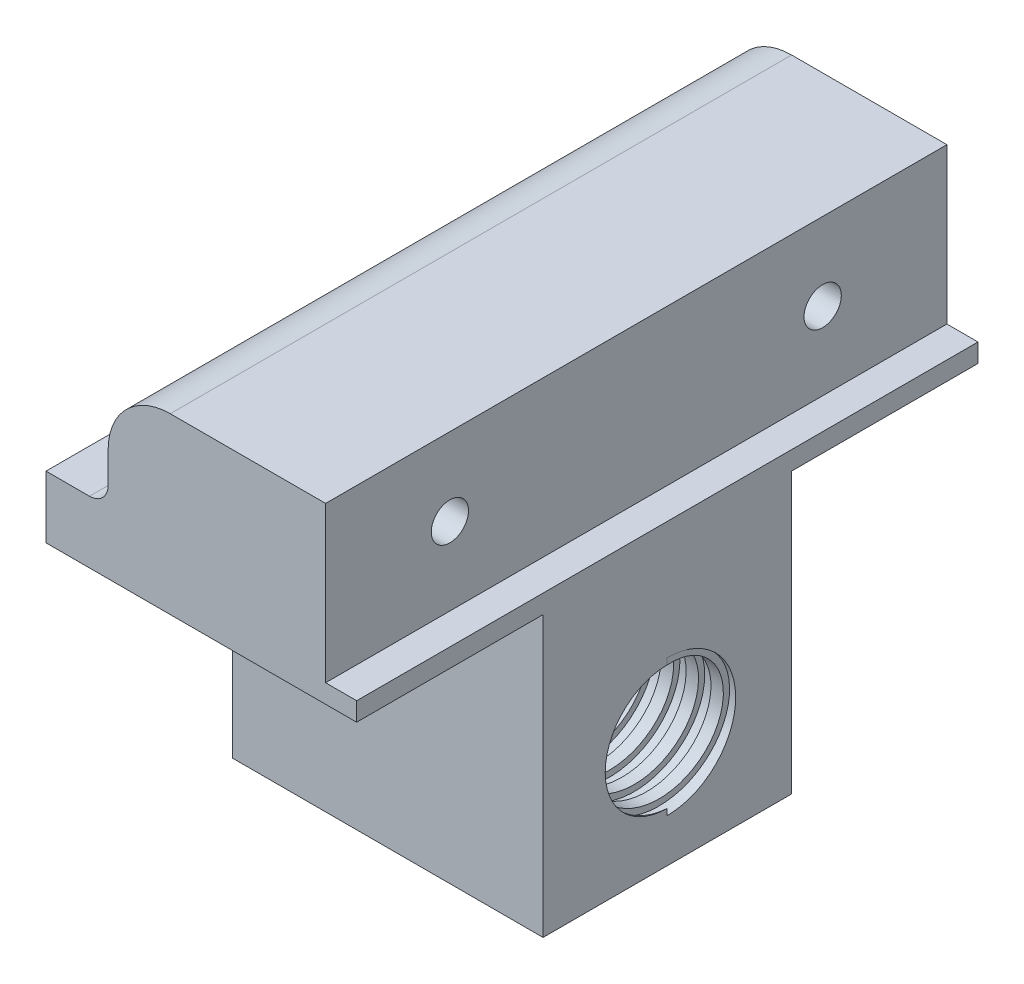
SolidWorks part; units mm, degrees
material "Gray Cast Iron (SN)"
ref_plane "Front Plane" through (0, 0, 0) normal (0, 0, 1) x (1, 0, 0)
ref_plane "Top Plane" through (0, 0, 0) normal (0, 1, 0) x (1, 0, 0)
ref_plane "Right Plane" through (0, 0, 0) normal (1, 0, 0) x (0, 0, -1)
sketch "Sketch1" plane through (0, 0, 0) normal (0, 0, 1) x (1, 0, 0)
  line L1 (-25.7736, -14.5358) -> (24.2264, -14.5358)
  line L2 (-25.7736, -14.5358) -> (-25.7736, -4.5358)
  line L3 (-5.7736, 13.4642) -> (19.2264, 13.4642)
  line L4 (24.2264, -14.5358) -> (24.2264, -11.5358)
  line L5 (-25.7736, -14.5358) -> (19.2264, 10.8433) construction
  line L6 (-15.7736, 9.4642) -> (24.2264, -14.5358) construction
  line L9 (-25.7736, -4.5358) -> (-18.7736, -4.5358)
  line L10 (-15.7736, 3.4642) -> (-15.7736, -1.5358)
  line L13 (24.2264, -11.5358) -> (19.2264, -11.5358)
  line L14 (19.2264, 13.4642) -> (19.2264, -11.5358)
  arc A0 (-5.7736, 13.4642) -> (-15.7736, 3.4642) centre (-5.7736, 3.4642) ccw
  arc A1 (-18.7736, -4.5358) -> (-15.7736, -1.5358) centre (-18.7736, -1.5358) ccw
  point P0 (0, 0)
  point P14 (-15.7736, 13.4642)
  dimension "D7" = 10
  dimension "D8" = 3
  dimension "D1" = 50
  dimension "D2" = 35
  dimension "D3" = 25
  dimension "D4" = 3
  dimension "D5" = 10
  dimension "D6" = 5
extrude "Boss-Extrude1" add sketch "Sketch1" along normal mid plane 100
sketch "Sketch2" plane through (0, -14.5358, 0) normal (0, -1, 0) x (1, 0, 0)
  line L0 (-25.7736, 50) -> (-25.7736, -50) construction
  line L1 (-25.7736, 20) -> (24.2264, 20)
  line L2 (-25.7736, 20) -> (-25.7736, -20)
  line L3 (-25.7736, -20) -> (24.2264, -20)
  line L4 (24.2264, 20) -> (24.2264, -20)
  line L5 (24.2264, 50) -> (24.2264, -50) construction
  line L6 (-25.7736, 50) -> (24.2264, 50) construction
  dimension "D1" = 40
  dimension "D2" = 30
extrude "Boss-Extrude2" add sketch "Sketch2" along normal blind 45
sketch "Sketch3" plane through (24.2264, 0, 0) normal (1, 0, 0) x (0, 0, -1)
  line L0 (-50, -14.5358) -> (-20, -14.5358) construction
  circle A0 centre (0, -41.5358) radius 10
  dimension "D1" = 20
  dimension "D2" = 27
extrude "Cut-Extrude1" cut sketch "Sketch3" against normal through all
sketch "Sketch4" plane through (24.2264, 0, 0) normal (1, 0, 0) x (0, 0, -1)
  circle A0 centre (0, -41.5358) radius 10 construction
  circle A1 centre (0, -41.5358) radius 10
curve "Helix/Spiral1" pitch 4 height 53 radius 10 centre (24.2264, -41.5358, 0) axis (-1, 0, 0) start towards (0, 0, -1)
ref_plane "Plane3" through (-28.7736, -51.5358, 0) normal (-0.0635, 0, 0.998) x (0.998, 0, 0.0635)
sketch "Sketch7" plane through (-28.7736, -51.5358, 0) normal (-0.0635, 0, 0.998) x (0.998, 0, 0.0635)
  line L1 (-1, -1) -> (1, -1)
  line L2 (-1, -1) -> (-1, 1)
  line L3 (-1, 1) -> (1, 1)
  line L4 (1, -1) -> (1, 1)
  line L5 (-1, -1) -> (1, 1) construction
  line L6 (-1, 1) -> (1, -1) construction
  point P0 (0, 0)
  dimension "D1" = 2
  dimension "D2" = 2
sweep "Cut-Sweep1" cut profiles "Sketch7" path "Helix/Spiral1" align with end faces yes
sketch "Sketch8" plane through (19.2264, 0, 0) normal (1, 0, 0) x (0, 0, -1)
  line L0 (50, -11.5358) -> (50, 13.4642) construction
  line L1 (-50, -14.5358) -> (-20, -14.5358) construction
  point P0 (-30, 0.9642)
  point P1 (30, 0.9642)
  dimension "D1" = 60
  dimension "D2" = 20
  dimension "D3" = 15.5
sketch "Sketch9" plane through (0, -59.5358, 0) normal (0, -1, 0) x (1, 0, 0)
  line L0 (24.2264, 20) -> (-25.7736, 20) construction
  line L1 (-25.7736, 20) -> (-25.7736, -20) construction
  point P0 (-0.7736, 12)
  point P1 (-0.7736, -12)
  dimension "D1" = 24
  dimension "D2" = 8
  dimension "D3" = 25
hole_wizard "Hole1" positions "3DSketch1" profile "Sketch10" legacy
sketch3d "3DSketch1"
  point P0 (19.2264, 0.9642, 30)
  point P3 (19.2264, 0.9642, -30)
  point P6 (-0.7736, -59.5358, 12)
  point P9 (-0.7736, -59.5358, -12)
sketch "Sketch10" plane through (19.2264, 0.9642, 30) normal (0, 1, 0) x (0, 0, -1)
  line L0 (0, 0) -> (0, 14.5022)
  line L1 (0, 14.5022) -> (2.5, 13)
  line L2 (2.5, 13) -> (2.5, 10)
  line L3 (2.5, 10) -> (3, 10)
  line L4 (3, 0) -> (0, 0)
  line L5 (0, -11.3109) -> (0, 121.1557) construction
  line L6 (0, 14.5022) -> (-2.5, 13) construction
  line L7 (3, 10) -> (3, 0)
  dimension "Depth" = 13
  dimension "Drill Angle" = 118
  dimension "Diameter" = 5
  dimension "C-Bore Diameter" = 6
  dimension "C-Bore Depth" = 10
